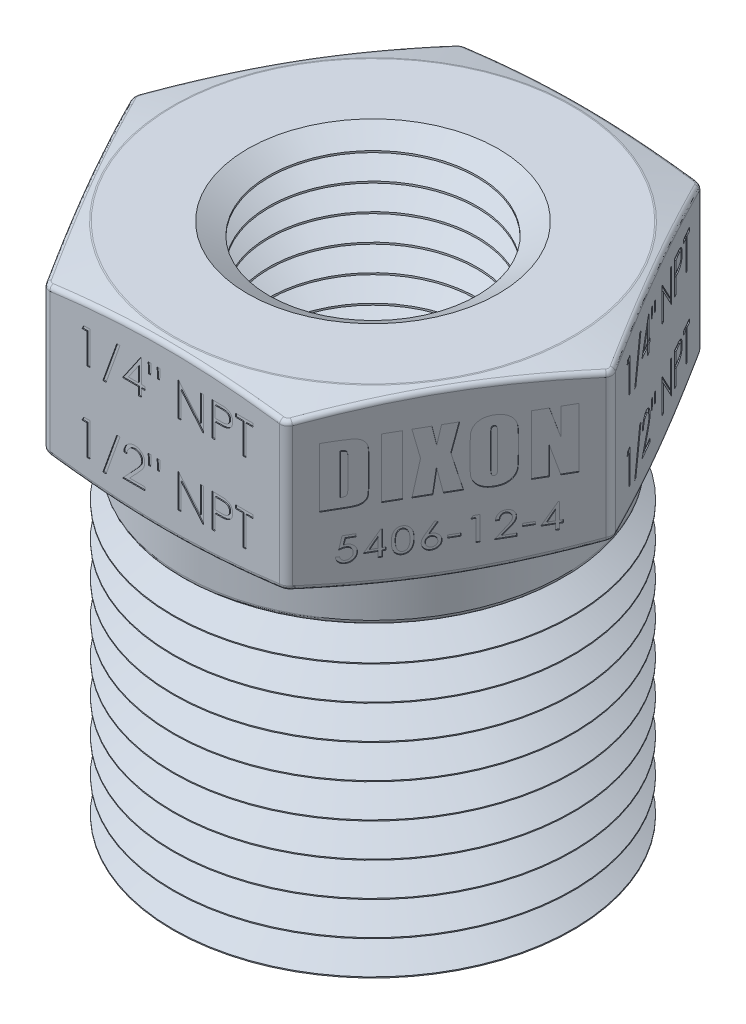
SolidWorks part; units mm, degrees
material "Plain Carbon Steel"
ref_plane "Front Plane" through (0, 0, 0) normal (0, 0, 1) x (1, 0, 0)
ref_plane "Top Plane" through (0, 0, 0) normal (0, 1, 0) x (1, 0, 0)
ref_plane "Right Plane" through (0, 0, 0) normal (1, 0, 0) x (0, 0, -1)
sketch "Sketch1" plane through (0, 0, 0) normal (0, 1, 0) x (1, 0, 0)
  line L1 (12.8316, 0) -> (6.4158, 11.1125)
  line L2 (6.4158, 11.1125) -> (-6.4158, 11.1125)
  line L3 (-6.4158, 11.1125) -> (-12.8316, 0)
  line L4 (-12.8316, 0) -> (-6.4158, -11.1125)
  line L5 (-6.4158, -11.1125) -> (6.4158, -11.1125)
  line L6 (6.4158, -11.1125) -> (12.8316, 0)
  circle A0 centre (0, 0) radius 11.1125 construction
  dimension "D1" = 22.225
extrude "Boss-Extrude1" add sketch "Sketch1" against normal blind 8.89
sketch "Sketch2" plane through (0, 0, 0) normal (0, 1, 0) x (1, 0, 0)
  circle A0 centre (0, 0) radius 10.668
  dimension "D1" = 21.336
extrude "Cut-Extrude2" cut sketch "Sketch2" against normal blind 8.89 draft 75 flip side to cut
sketch "Sketch3" plane through (0, -8.89, 0) normal (0, -1, 0) x (1, 0, 0)
  circle A0 centre (0, 0) radius 10.668 construction
  circle A1 centre (0, 0) radius 10.668
extrude "Cut-Extrude3" cut sketch "Sketch3" against normal blind 8.89 draft 75 flip side to cut
sketch "Sketch4" plane through (0, -8.89, 0) normal (0, -1, 0) x (1, 0, 0)
  circle A0 centre (0, 0) radius 10.2235
  dimension "D1" = 20.447
extrude "Boss-Extrude2" add sketch "Sketch4" along normal blind 3.175
sketch "Sketch5" plane through (0, -12.065, 0) normal (0, -1, 0) x (1, 0, 0)
  circle A0 centre (0, 0) radius 10.668
  dimension "D1" = 21.336
extrude "Boss-Extrude3" add sketch "Sketch5" along normal offset from surface (16.256 mm away) 28.321 up to face at (0, 0, 10.668)
sketch "Sketch6" plane through (0, 0, 0) normal (0, 0, 1) x (1, 0, 0)
  line L0 (0, 0) -> (0, -28.321) construction
  line L1 (10.668, 0) -> (-10.668, 0) construction
  line L2 (0, -28.321) -> (9.144, -28.321) construction
  line L3 (9.144, -28.321) -> (10.7152, -28.321) construction
  line L4 (10.7152, -28.321) -> (12.5295, -28.321) construction
  line L5 (12.5295, -27.4139) -> (12.5295, -29.2281)
  line L6 (10.7152, -27.4139) -> (10.7152, -29.2281) construction
  line L7 (12.5295, -27.4139) -> (10.7152, -27.4139)
  line L8 (10.7152, -27.4139) -> (9.144, -28.321)
  line L9 (9.144, -28.321) -> (10.7152, -29.2281)
  line L10 (10.7152, -29.2281) -> (12.5295, -29.2281)
  line L11 (-10.668, -28.321) -> (10.668, -28.321) construction
  dimension "D1" = 60
  dimension "D2" = 1.8143
  dimension "D3" = 9.144
revolve "Cut-Revolve1" cut sketch "Sketch6" angle 360 about L0
pattern_linear "LPattern1" count 10 spacing 1.8143 along (0, 1, 0) of "Cut-Revolve1"
sketch "Sketch7" plane through (0, 0, 0) normal (0, 1, 0) x (1, 0, 0)
  circle A0 centre (0, 0) radius 5.5562
  dimension "D1" = 11.1125
extrude "Cut-Extrude4" cut sketch "Sketch7" against normal up to surface (28.321 mm away) up to face at (0, -28.321, 9.144)
sketch "Sketch8" plane through (0, 0, 0) normal (0, 0, 1) x (1, 0, 0)
  line L0 (0, 0) -> (4.064, 0) construction
  line L1 (4.064, 0) -> (5.4751, 0) construction
  line L2 (5.4751, 0) -> (6.6972, 0) construction
  line L3 (4.064, 0.7056) -> (4.064, -0.7056)
  line L4 (5.4751, 0.7056) -> (5.4751, -0.7056) construction
  line L5 (4.064, 0.7056) -> (5.4751, 0.7056)
  line L6 (5.4751, 0.7056) -> (6.6972, 0)
  line L7 (6.6972, 0) -> (5.4751, -0.7056)
  line L8 (5.4751, -0.7056) -> (4.064, -0.7056)
  line L9 (5.5562, 0) -> (-5.5562, 0) construction
  line L10 (0, 0) -> (0, -28.321) construction
  line L11 (-5.5562, -28.321) -> (5.5562, -28.321) construction
  dimension "D1" = 1.4111
  dimension "D2" = 60
  dimension "D3" = 4.064
revolve "Cut-Revolve2" cut sketch "Sketch8" angle 360 about L10
pattern_linear "LPattern2" count 10 spacing 1.4111 along (0, -1, 0) of "Cut-Revolve2"
fillet "Fillet1" radius 0.508 6 edges at (-6.4158, -4.445, 11.1125) (-12.8316, -4.445, 0) (-6.4158, -4.445, -11.1125) (6.4158, -4.445, -11.1125) (12.8316, -4.445, 0) (6.4158, -4.445, 11.1125)
fillet "Fillet2" radius 0.254 26 edges at (0, -8.89, -10.668) (6.3155, -8.3325, 11.0744) (12.7485, -8.3325, 0.0679) (6.433, -8.3325, -11.0066) (-6.3155, -8.3325, -11.0744) (-12.7485, -8.3325, -0.0679) (-6.433, -8.3325, 11.0066) (0, 0, 10.668) (-12.7485, -0.5575, 0.0679) (-6.433, -0.5575, -11.0066) (6.3155, -0.5575, -11.0744) (12.7485, -0.5575, -0.0679) (6.433, -0.5575, 11.0066) (-6.3155, -0.5575, 11.0744)
fillet "Fillet3" radius 0.254 2 edges at (0, -11.3692, 10.2235) (0, -8.89, 10.2235)
sketch "Sketch10" plane through (0, -28.321, 0) normal (0, -1, 0) x (1, 0, 0)
  circle A0 centre (0, 0) radius 6.731
  dimension "D1" = 13.462
extrude "Cut-Extrude6" cut sketch "Sketch10" against normal blind 14.224
chamfer "Chamfer1" distance 1.5875 angle 45 1 edges at (0, -14.097, -6.731)
chamfer "Chamfer2" distance 2.032 angle 30 1 edges at (0, -28.321, -6.731) first distance on face at (0, -15.6845, -6.731)
sketch "Sketch9" plane through (0, 0, 11.1125) normal (0, 0, 1) x (1, 0, 0)
  line L0 (0, 0) -> (0, -3.2046) construction
  line L1 (0, -3.2046) -> (0, -7.4339) construction
  line L2 (-6.1225, -3.2046) -> (6.1225, -3.2046) construction
  line L3 (-6.1225, -7.4339) -> (6.1225, -7.4339) construction
  line L4 (-6.1225, -0.7446) -> (-6.1225, -8.1454) construction
  text T0 "1/4\" NPT" font "Century Gothic" height 1.778
  text T1 "1/2\" NPT" font "Century Gothic" height 1.778
extrude "Cut-Extrude5" cut sketch "Sketch9" against normal blind 0.0508
pattern_circular "CirPattern1" count 3 over 360 about axis through (0, -12.065, 0) along (0, 1, 0) of "Cut-Extrude5"
sketch "Sketch11" plane through (9.6237, 0, 5.5562) normal (0.866, 0, 0.5) x (0.5, 0, -0.866)
  line L0 (0, 0) -> (0, -4.9314) construction
  line L1 (-6.1225, -4.9314) -> (6.1225, -4.9314) construction
  line L2 (-6.1225, -0.7446) -> (-6.1225, -8.1454) construction
  line L3 (0, -4.9314) -> (0, -7.4534) construction
  line L4 (-6.1225, -7.4534) -> (6.1225, -7.4534) construction
  line L5 (6.1225, -8.1454) -> (6.1225, -0.7446) construction
  text T0 "DIXON" font "Impact" height 3.175
  text T1 "5406-12-4" font "Century Gothic" height 1.27
extrude "Cut-Extrude7" cut sketch "Sketch11" against normal blind 0.0508
pattern_circular "CirPattern2" count 3 over 360 about axis through (0, -12.065, 0) along (0, 1, 0) of "Cut-Extrude7"
